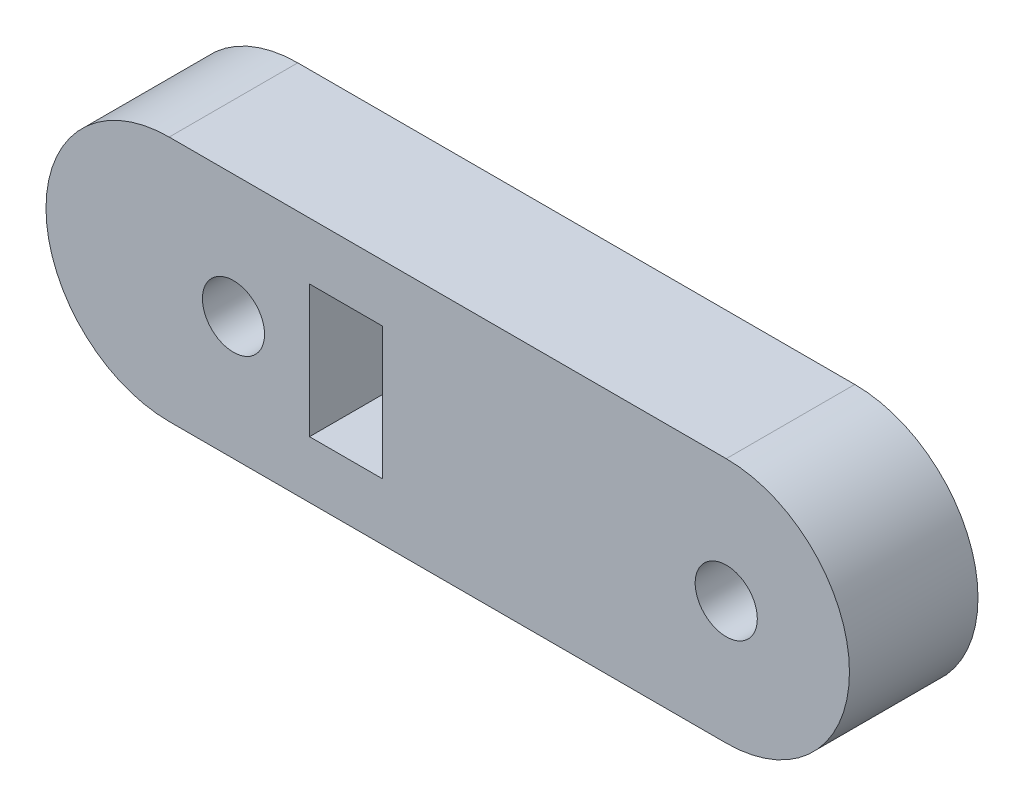
SolidWorks part; units mm, degrees
material "Acrylic (Medium-high impact)"
ref_plane "Front Plane" through (0, 0, 0) normal (0, 0, 1) x (1, 0, 0)
ref_plane "Top Plane" through (0, 0, 0) normal (0, 1, 0) x (1, 0, 0)
ref_plane "Right Plane" through (0, 0, 0) normal (1, 0, 0) x (0, 0, -1)
sketch "Sketch1" plane through (0, 0, 0) normal (0, 0, 1) x (1, 0, 0)
  line L0 (595.0214, 463.5696) -> (595.0214, 460.4829) construction
  line L1 (595.0214, 460.4829) -> (595.0214, 457.3962) construction
  line L2 (596.7214, 463.5696) -> (596.7214, 457.3962)
  line L3 (596.7214, 457.3962) -> (593.3214, 457.3962)
  line L4 (593.3214, 457.3962) -> (593.3214, 463.5696)
  line L5 (593.3214, 463.5696) -> (596.7214, 463.5696)
  line L6 (595.0214, 463.5696) -> (595.0214, 466.2329) construction
  line L7 (589.7714, 460.4829) -> (589.7714, 466.2329) construction
  line L8 (589.7714, 460.4829) -> (589.7714, 454.7329) construction
  line L9 (612.7714, 460.4829) -> (612.7714, 466.2329) construction
  line L10 (612.7714, 460.4829) -> (612.7714, 454.7329) construction
  line L11 (589.7714, 466.2329) -> (612.7714, 466.2329)
  line L12 (589.7714, 454.7329) -> (612.7714, 454.7329)
  line L13 (593.3214, 460.4829) -> (595.0214, 460.4829) construction
  line L14 (595.0214, 460.4829) -> (596.7214, 460.4829) construction
  line L15 (589.7714, 460.4829) -> (595.0214, 460.4829) construction
  line L16 (612.7714, 460.4829) -> (595.0214, 460.4829) construction
  line L17 (595.0214, 460.4829) -> (589.7714, 460.4829) construction
  line L18 (589.7714, 466.2329) -> (586.7714, 466.2329)
  line L19 (589.7714, 454.7329) -> (586.7714, 454.7329)
  circle A0 centre (589.7714, 460.4829) radius 1.45
  circle A1 centre (612.7714, 460.4829) radius 1.45
  arc A2 (586.7714, 466.2329) -> (586.7714, 454.7329) centre (586.7714, 460.4829) ccw
  arc A3 (612.7714, 454.7329) -> (612.7714, 466.2329) centre (612.7714, 460.4829) ccw
  point P19 (591.2214, 460.4829)
  dimension "D1" = 2.1
  dimension "D2" = 2.9
  dimension "D3" = 23
  dimension "D4" = 11.5
extrude "Boss-Extrude1" add sketch "Sketch1" along normal blind 6
